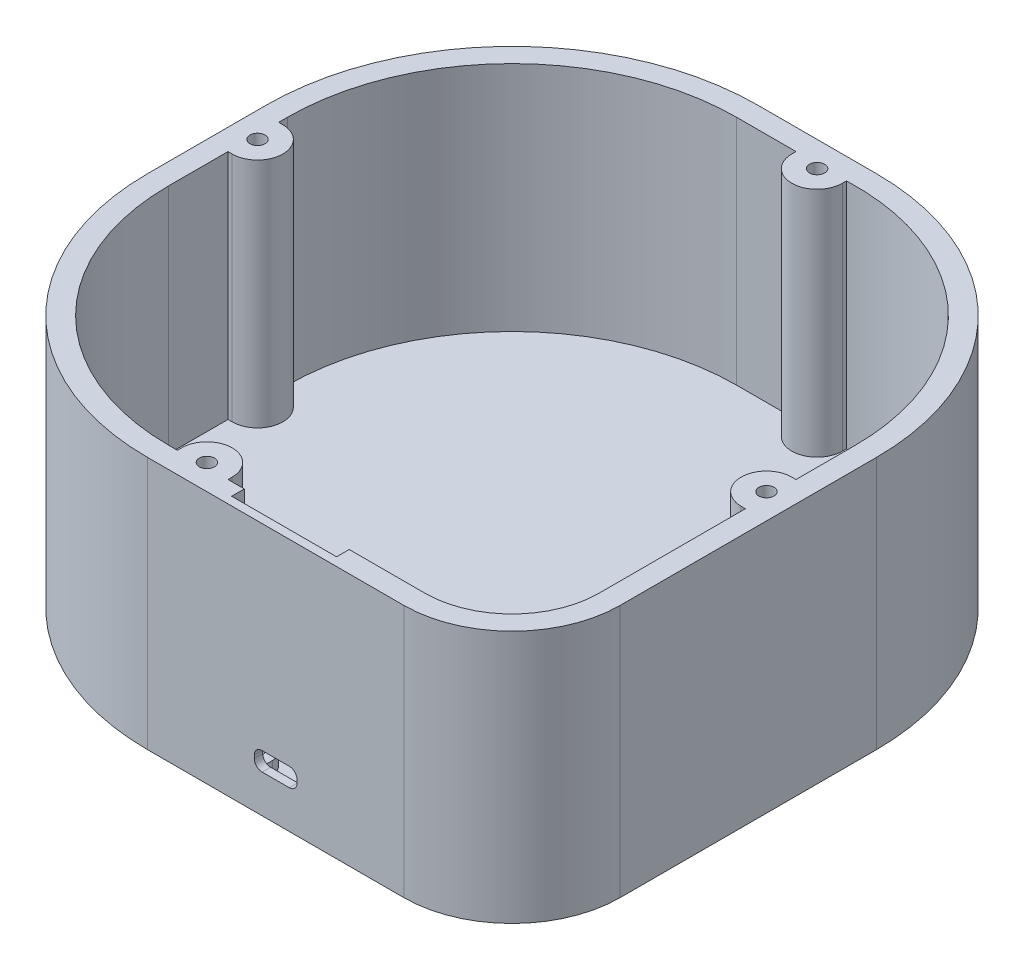
SolidWorks part; units mm, degrees
material "ABS"
ref_plane "Front Plane" through (0, 0, 0) normal (0, 0, 1) x (1, 0, 0)
ref_plane "Top Plane" through (0, 0, 0) normal (0, 1, 0) x (1, 0, 0)
ref_plane "Right Plane" through (0, 0, 0) normal (1, 0, 0) x (0, 0, -1)
sketch "Sketch1" plane through (0, 0, 0) normal (0, 1, 0) x (1, 0, 0)
  line L0 (58.25, 139.6405) -> (72.3202, 139.6405)
  line L1 (58.25, 0) -> (118.9905, 0)
  line L2 (0, 58.25) -> (0, 86.3905)
  line L3 (58.25, 144.6405) -> (86.3905, 144.6405)
  line L4 (144.6405, 25.65) -> (144.6405, 86.3905)
  line L5 (139.6405, 25.65) -> (139.6405, 60.3202)
  line L6 (58.25, 5) -> (60.3202, 5)
  line L7 (5, 58.25) -> (5, 72.3202)
  line L8 (101.0502, 5) -> (118.9905, 5)
  line L9 (77.1902, 2) -> (100.0502, 2) construction
  line L10 (77.1902, 2) -> (77.1902, 52.8) construction
  line L11 (77.1902, 52.8) -> (100.0502, 52.8) construction
  line L12 (100.0502, 2) -> (100.0502, 52.8) construction
  line L13 (58.25, 5) -> (118.9905, 5) construction
  line L15 (76.1902, 53.8) -> (101.0502, 53.8) construction
  line L18 (76.1902, 1) -> (101.0502, 1) construction
  line L19 (101.0502, 1) -> (101.0502, 53.8) construction
  line L20 (101.0502, 5) -> (101.0502, 2)
  line L21 (101.0502, 2) -> (100.0502, 2)
  line L22 (76.1902, 5) -> (76.1902, 2)
  line L23 (76.1902, 1) -> (76.1902, 53.8) construction
  line L24 (76.1902, 2) -> (77.1902, 2)
  line L25 (93.9702, 4.54) -> (93.9702, 2)
  line L26 (83.2702, 4.54) -> (83.2702, 2)
  line L27 (77.1902, 2) -> (100.0502, 2)
  line L28 (76.1902, 53.8) -> (76.1902, 5) construction
  line L29 (101.0502, 53.8) -> (101.0502, 5) construction
  line L30 (79.7302, 50.26) -> (97.5102, 50.26) construction
  line L31 (72.3202, 144.6405) -> (72.3202, 0) construction
  line L32 (5, 72.3202) -> (139.6405, 72.3202) construction
  line L33 (72.3202, 6) -> (72.3202, 5)
  line L34 (60.3202, 6) -> (60.3202, 5)
  line L35 (72.3202, 5) -> (76.1902, 5)
  line L36 (139.6405, 72.3202) -> (139.6405, 86.3905)
  line L37 (139.6405, 25.65) -> (139.6405, 86.3905) construction
  line L38 (138.6405, 72.3202) -> (139.6405, 72.3202)
  line L39 (58.25, 139.6405) -> (86.3905, 139.6405) construction
  line L40 (5, 84.3202) -> (5, 86.3905)
  line L41 (5, 58.25) -> (5, 86.3905) construction
  line L42 (6, 72.3202) -> (5, 72.3202)
  line L43 (6, 84.3202) -> (5, 84.3202)
  line L44 (72.3202, 138.6405) -> (72.3202, 139.6405)
  line L45 (84.3202, 138.6405) -> (84.3202, 139.6002)
  line L46 (138.6405, 60.3202) -> (139.6405, 60.3202)
  arc A0 (58.25, 0) -> (0, 58.25) centre (58.25, 58.25) cw
  arc A1 (86.3905, 144.6405) -> (144.6405, 86.3905) centre (86.3905, 86.3905) cw
  arc A2 (0, 86.3905) -> (58.25, 144.6405) centre (58.25, 86.3905) cw
  arc A3 (118.9905, 0) -> (144.6405, 25.65) centre (118.9905, 25.65) ccw
  arc A4 (5, 86.3905) -> (58.25, 139.6405) centre (58.25, 86.3905) cw
  arc A5 (84.3202, 139.6002) -> (139.6405, 86.3905) centre (86.3905, 86.3905) cw
  arc A6 (118.9905, 5) -> (139.6405, 25.65) centre (118.9905, 25.65) ccw
  arc A7 (58.25, 5) -> (5, 58.25) centre (58.25, 58.25) cw
  circle A8 centre (79.7302, 50.26) radius 1.143 construction
  circle A9 centre (97.5102, 50.26) radius 1.143 construction
  circle A10 centre (97.5102, 4.54) radius 1.27 construction
  circle A11 centre (79.7302, 4.54) radius 1.27 construction
  circle A12 centre (79.7302, 50.26) radius 2.143
  circle A13 centre (97.5102, 50.26) radius 2.143
  arc A14 (83.2702, 4.54) -> (76.1902, 4.54) centre (79.7302, 4.54) ccw
  arc A15 (101.0502, 4.54) -> (93.9702, 4.54) centre (97.5102, 4.54) ccw
  circle A16 centre (79.7302, 4.54) radius 1.25
  circle A17 centre (97.5102, 4.54) radius 1.25
  circle A18 centre (6, 78.3202) radius 3.5
  circle A19 centre (78.3202, 138.6405) radius 3.5
  circle A20 centre (138.6405, 66.3202) radius 3.5
  circle A21 centre (66.3202, 6) radius 3.5
  arc A22 (6, 72.3202) -> (6, 84.3202) centre (6, 78.3202) ccw
  arc A23 (72.3202, 138.6405) -> (84.3202, 138.6405) centre (78.3202, 138.6405) ccw
  arc A24 (138.6405, 72.3202) -> (138.6405, 60.3202) centre (138.6405, 66.3202) ccw
  arc A25 (72.3202, 6) -> (60.3202, 6) centre (66.3202, 6) ccw
  arc A26 (86.3905, 139.6405) -> (139.6405, 86.3905) centre (86.3905, 86.3905) cw construction
  circle A27 centre (6, 78.3202) radius 1.8
  circle A28 centre (78.3202, 138.6405) radius 1.8
  circle A29 centre (138.6405, 66.3202) radius 1.8
  circle A30 centre (66.3202, 6) radius 1.8
  point P7 (0, 0)
  point P42 (88.6202, 50.26)
  point P43 (88.6202, 2)
  point P46 (77.1902, 27.4)
  point P48 (88.6202, 0)
  point P62 (88.6202, 52.8)
  point P71 (72.3202, 72.3202)
  point P75 (72.3202, 72.3202)
  dimension "D2" = 58.25
  dimension "D3" = 25.65
  dimension "D7" = 2.286
  dimension "D8" = 2.54
  dimension "D9" = 17.78
  dimension "D10" = 45.72
  dimension "D17" = 2.5
  dimension "D11" = 7
  dimension "D18" = 6
  dimension "D25" = 6
  dimension "D26" = 3.6
  dimension "D1" = 144.6405
  dimension "D5" = 22.86
  dimension "D6" = 50.8
  dimension "D12" = 2
  dimension "D13" = 0
  dimension "D14" = 22.86
  dimension "D16" = 1
  dimension "D19" = 6
  dimension "D20" = 6
  dimension "D21" = 6
  dimension "D22" = 6
  dimension "D4" = 5
  dimension "D15" = 1
extrude "Boss-Extrude1" add sketch "Sketch1" along normal blind 60 contours L1 A3 L4 A1 L3 A2 L2 A0 L6 A7 L7 A4 L0 A5 L5 A6 L8 L20 L21 L27 L24 L22 | A7 L7 L2 A0 | L6 L1 | L7 L2 | L7 A4 L0 L3 A2 L2 | L3 L0 | L0 A5 A1 L3 | L5 L4 region at (18.5074, 0, -18.5074)
extrude "Boss-Extrude2" add sketch "Sketch1<2>" along normal blind 5 contours A12 | A13 | A15 L20 L8 A6 L5 A5 L0 A4 L7 A7 L6 L22 A14 L26 L27 L25 A13 A12 | L26 A14 L22 L24 L27 A16 | A17 | L20 A15 L25 L27 L21 A17 | A16 region at (74.0494, 0, -70.5981) region at (100.9569, 0, -3.27) region at (79.7302, 0, -7.9867) region at (79.7302, 0, -50.26) region at (97.5102, 0, -50.26) region at (79.7302, 0, -4.54) region at (97.5102, 0, -4.54)
sketch "Sketch1<2>" plane through (0, 0, 0) normal (0, 1, 0) x (1, 0, 0) same geometry as "Sketch1"
extrude "Boss-Extrude3" add sketch "Sketch1<4>" along normal blind 3 from surface contours L26 A14 L22 L24 L27 A16 | L20 A15 L25 L27 L21 A17 | A13 | A12 region at (100.9569, 0, -3.27) region at (79.7302, 0, -7.9867) region at (79.7302, 0, -50.26) region at (97.5102, 0, -50.26) starting at face at (75.1822, 5, -58.7001)
sketch "Sketch1<4>" plane through (0, 0, 0) normal (0, 1, 0) x (1, 0, 0) same geometry as "Sketch1"
sketch "Sketch2" plane through (0, 0, -2) normal (0, 0, -1) x (-1, 0, 0)
  line L0 (-88.6202, 5) -> (-88.6202, 60) construction
  line L1 (-83.2702, 5) -> (-93.9702, 5) construction
  line L2 (-101.0502, 60) -> (-76.1902, 60) construction
  line L3 (-91.8402, 12.8) -> (-85.4002, 12.8) construction
  line L4 (-91.8402, 9.59) -> (-85.4002, 9.59) construction
  line L5 (-84.1502, 11.55) -> (-84.1502, 10.84) construction
  line L6 (-93.0902, 11.55) -> (-93.0902, 10.84) construction
  line L7 (-91.8402, 13.4) -> (-85.4002, 13.4)
  line L8 (-93.6902, 11.55) -> (-93.6902, 10.84)
  line L9 (-91.8402, 8.99) -> (-85.4002, 8.99)
  line L10 (-83.5502, 11.55) -> (-83.5502, 10.84)
  arc A0 (-93.0902, 11.55) -> (-91.8402, 12.8) centre (-91.8402, 11.55) cw construction
  arc A1 (-93.0902, 10.84) -> (-91.8402, 9.59) centre (-91.8402, 10.84) ccw construction
  arc A2 (-85.4002, 9.59) -> (-84.1502, 10.84) centre (-85.4002, 10.84) ccw construction
  arc A3 (-84.1502, 11.55) -> (-85.4002, 12.8) centre (-85.4002, 11.55) ccw construction
  arc A4 (-83.5502, 11.55) -> (-85.4002, 13.4) centre (-85.4002, 11.55) ccw
  arc A5 (-93.6902, 11.55) -> (-91.8402, 13.4) centre (-91.8402, 11.55) cw
  arc A6 (-93.6902, 10.84) -> (-91.8402, 8.99) centre (-91.8402, 10.84) ccw
  arc A7 (-85.4002, 8.99) -> (-83.5502, 10.84) centre (-85.4002, 10.84) ccw
  point P9 (-88.6202, 12.8)
  point P12 (-88.6202, 9.59)
  dimension "D1" = 1.25
  dimension "D2" = 0.71
  dimension "D3" = 6.44
  dimension "D4" = 4.59
  dimension "D5" = 0.6
extrude "Cut-Extrude1" cut sketch "Sketch2" against normal up to next
extrude "Boss-Extrude4" add sketch "Sketch1<6>" against normal blind 3 from surface contours A18 A27 | A19 A28 | A20 A29 | A21 A30 region at (2.599, 0, -78.3202) region at (74.9192, 0, -138.6405) region at (135.2395, 0, -66.3202) region at (62.9192, 0, -6) starting at face at (75.5513, 60, -69.0892)
sketch "Sketch1<6>" plane through (0, 0, 0) normal (0, 1, 0) x (1, 0, 0) same geometry as "Sketch1"
